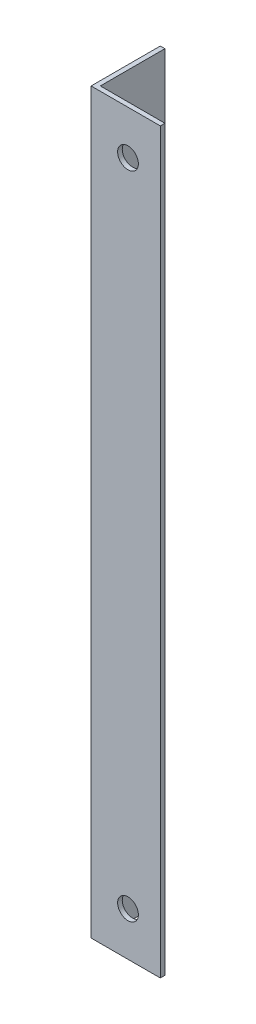
SolidWorks part; units mm, degrees
material "1060 Сплав"
ref_plane "Спереди" through (0, 0, 0) normal (0, 0, 1) x (1, 0, 0)
ref_plane "Сверху" through (0, 0, 0) normal (0, 1, 0) x (1, 0, 0)
ref_plane "Справа" through (0, 0, 0) normal (1, 0, 0) x (0, 0, -1)
sketch "Эскиз1" plane through (0, 0, 0) normal (0, 1, 0) x (1, 0, 0)
  line L0 (0, 0) -> (0, 15)
  line L1 (0, 15) -> (1, 15)
  line L2 (1, 15) -> (1, 1)
  line L3 (1, 1) -> (15, 1)
  line L4 (15, 1) -> (15, 0)
  line L5 (15, 0) -> (0, 0)
  dimension "D1" = 1
  dimension "D2" = 15
extrude "Бобышка-Вытянуть1" add sketch "Эскиз1" along normal blind 160
sketch "Эскиз2" plane through (0, 0, -1) normal (0, 0, -1) x (-1, 0, 0)
  line L0 (-8, 0) -> (-8, 9.5) construction
  line L1 (-15, 0) -> (-1, 0) construction
  circle A0 centre (-8, 9.5) radius 2.25
  dimension "D2" = 4.5
  dimension "D1" = 9.5
extrude "Вырез-Вытянуть1" cut sketch "Эскиз2" against normal through all
sketch "Эскиз4" plane through (0, 0, -1) normal (0, 0, -1) x (-1, 0, 0)
  line L0 (-8, 160) -> (-8, 150.5) construction
  line L1 (-15, 160) -> (-1, 160) construction
  circle A0 centre (-8, 150.5) radius 2.25
  dimension "D2" = 4.5
  dimension "D1" = 9.5
extrude "Вырез-Вытянуть3" cut sketch "Эскиз4" against normal through all
